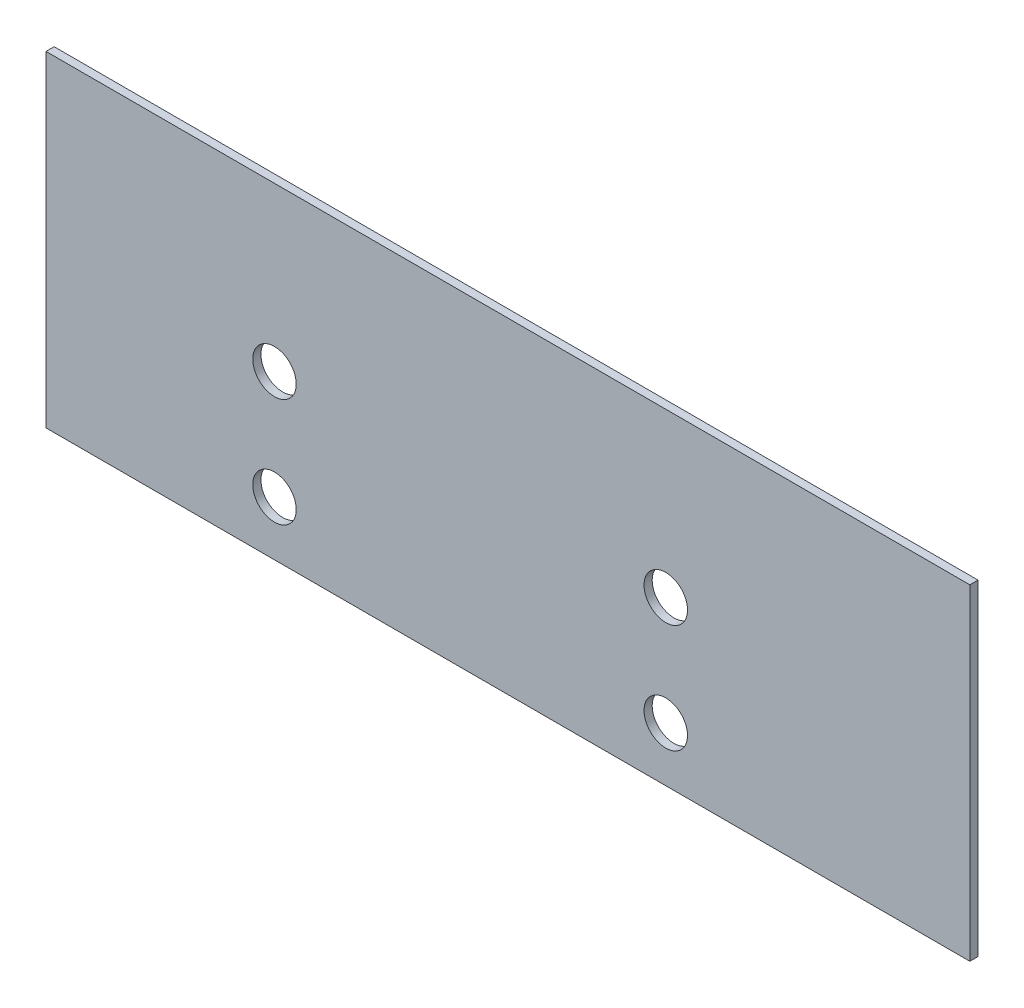
SolidWorks part; units mm, degrees
material "AISI 316 Chapa de acero inoxidable (SS)"
ref_plane "Alzado" through (0, 0, 0) normal (0, 0, 1) x (1, 0, 0)
ref_plane "Planta" through (0, 0, 0) normal (0, 1, 0) x (1, 0, 0)
ref_plane "Vista lateral" through (0, 0, 0) normal (1, 0, 0) x (0, 0, -1)
sketch "Croquis1" plane through (0, 0, 0) normal (0, 0, 1) x (1, 0, 0)
  line L1 (-85, -30) -> (85, -30)
  line L2 (-85, -30) -> (-85, 30)
  line L3 (-85, 30) -> (85, 30)
  line L4 (85, -30) -> (85, 30)
  line L5 (-85, -30) -> (85, 30) construction
  line L6 (-85, 30) -> (85, -30) construction
  point P0 (0, 0)
  dimension "D1" = 60
  dimension "D2" = 170
extrude "Saliente-Extruir1" add sketch "Croquis1" along normal blind 1.5
sketch "Croquis2" plane through (0, 0, 1.5) normal (0, 0, 1) x (1, 0, 0)
  circle A0 centre (-42.9549, -20) radius 4 construction
  circle A1 centre (-42.9549, 0) radius 4 construction
  circle A2 centre (29.0451, -20) radius 4 construction
  circle A3 centre (29.0451, 0) radius 4 construction
  circle A4 centre (-42.9549, -20) radius 4
  circle A5 centre (-42.9549, 0) radius 4
  circle A6 centre (29.0451, -20) radius 4
  circle A7 centre (29.0451, 0) radius 4
extrude "Cortar-Extruir1" cut sketch "Croquis2" against normal up to surface (1.5 mm away) up to face at (0, 0, 0)
